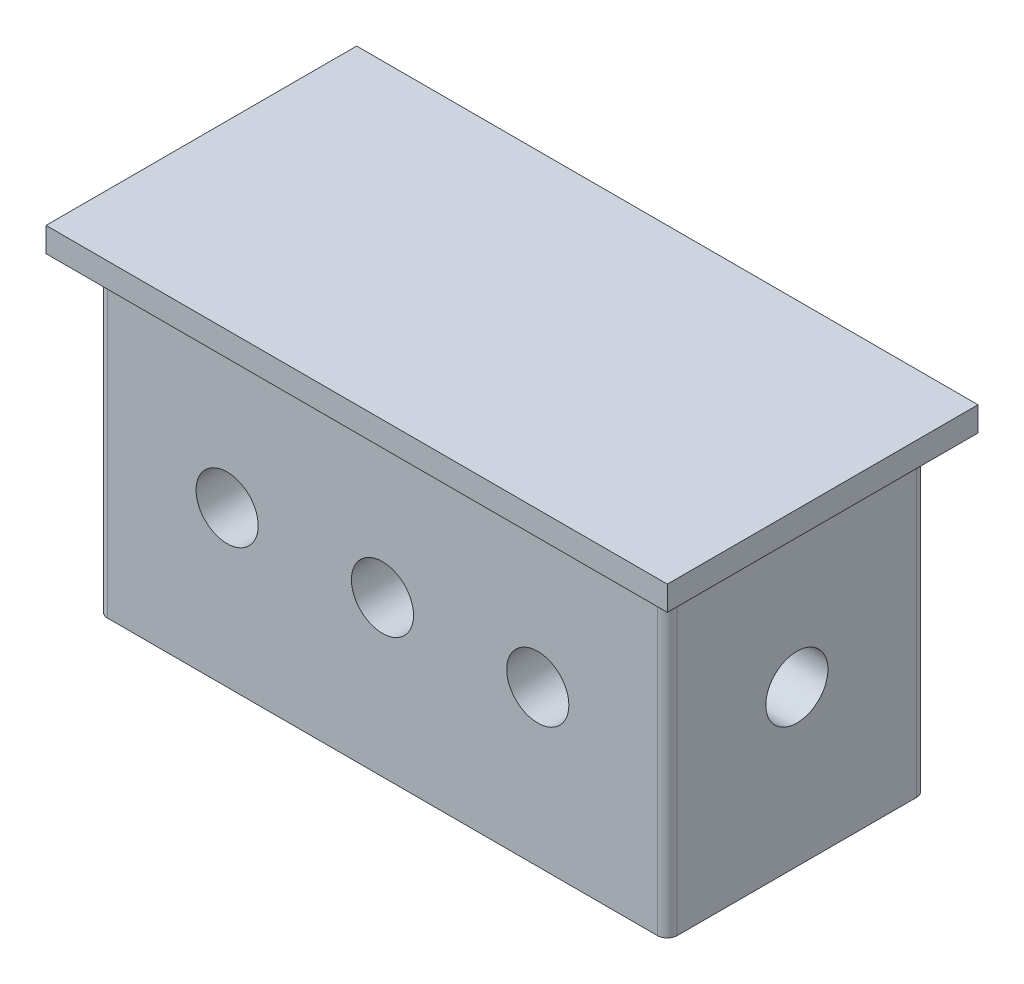
SolidWorks part; units mm, degrees
material "Nylon 101"
ref_plane "Front Plane" through (0, 0, 0) normal (0, 0, 1) x (1, 0, 0)
ref_plane "Top Plane" through (0, 0, 0) normal (0, 1, 0) x (1, 0, 0)
ref_plane "Right Plane" through (0, 0, 0) normal (1, 0, 0) x (0, 0, -1)
sketch "Sketch2" plane through (0, 0, 0) normal (0, 1, 0) x (1, 0, 0)
  line L1 (0, 0) -> (50.8, 0)
  line L2 (0, 0) -> (0, 25.4)
  line L3 (0, 25.4) -> (50.8, 25.4)
  line L12 (50.8, 0) -> (50.8, 25.4)
  line L14 (2.1082, 23.2918) -> (48.6918, 23.2918)
  line L15 (48.6918, 2.1082) -> (48.6918, 23.2918)
  line L16 (2.1082, 2.1082) -> (48.6918, 2.1082)
  line L17 (2.1082, 2.1082) -> (2.1082, 23.2918)
  dimension "D1" = 50.8
  dimension "D3" = 25.4
  dimension "D2" = 2.1082
extrude "Boss-Extrude2" add sketch "Sketch2" along normal blind 2 separate body contours L17 L16 L15 L14 | L16 L17 L14 L15 region at (0.568, 0, -12.7) region at (25.4, 0, -12.7)
extrude "Boss-Extrude3" add sketch "Sketch2<4>" against normal blind 25.4 contours L17 L16 L15 L14 region at (25.4, 0, -12.7)
sketch "Sketch2<4>" plane through (0, 0, 0) normal (0, 1, 0) x (1, 0, 0) same geometry as "Sketch2"
fillet "Fillet3" radius 0.8106 4 edges at (2.1082, -12.7, -23.2918) (48.6918, -12.7, -2.1082) (2.1082, -12.7, -2.1082) (48.6918, -12.7, -23.2918)
sketch "Sketch3" plane through (48.6918, 0, 0) normal (1, 0, 0) x (0, 0, -1)
  line L0 (2.9188, 0) -> (22.4812, 0) construction
  line L1 (2.9188, -25.4) -> (22.4812, -25.4) construction
  line L3 (12.7, 0) -> (12.7, -25.4) construction
  circle A0 centre (12.7, -12.7) radius 2.54
  dimension "D3" = 5.08
  dimension "D1" = 12.7
extrude "Cut-Extrude1" cut sketch "Sketch3" against normal through all
sketch "Sketch4" plane through (0, 0, -23.2918) normal (0, 0, -1) x (-1, 0, 0)
  line L0 (-47.8812, -12.7) -> (-2.9188, -12.7) construction
  line L1 (-47.8812, 0) -> (-47.8812, -25.4) construction
  line L2 (-2.9188, -25.4) -> (-2.9188, 0) construction
  line L3 (-2.9188, 0) -> (-47.8812, 0) construction
  circle A0 centre (-25.4, -12.7) radius 2.54
  circle A1 centre (-38.1, -12.7) radius 2.54
  circle A2 centre (-12.7, -12.7) radius 2.54
  dimension "D2" = 5.08
  dimension "D1" = 12.7
  dimension "D3" = 12.7
  dimension "D4" = 12.7
extrude "Cut-Extrude2" cut sketch "Sketch4" against normal through all
equation "\"D2@Sketch2\"=0.063+0.02"
